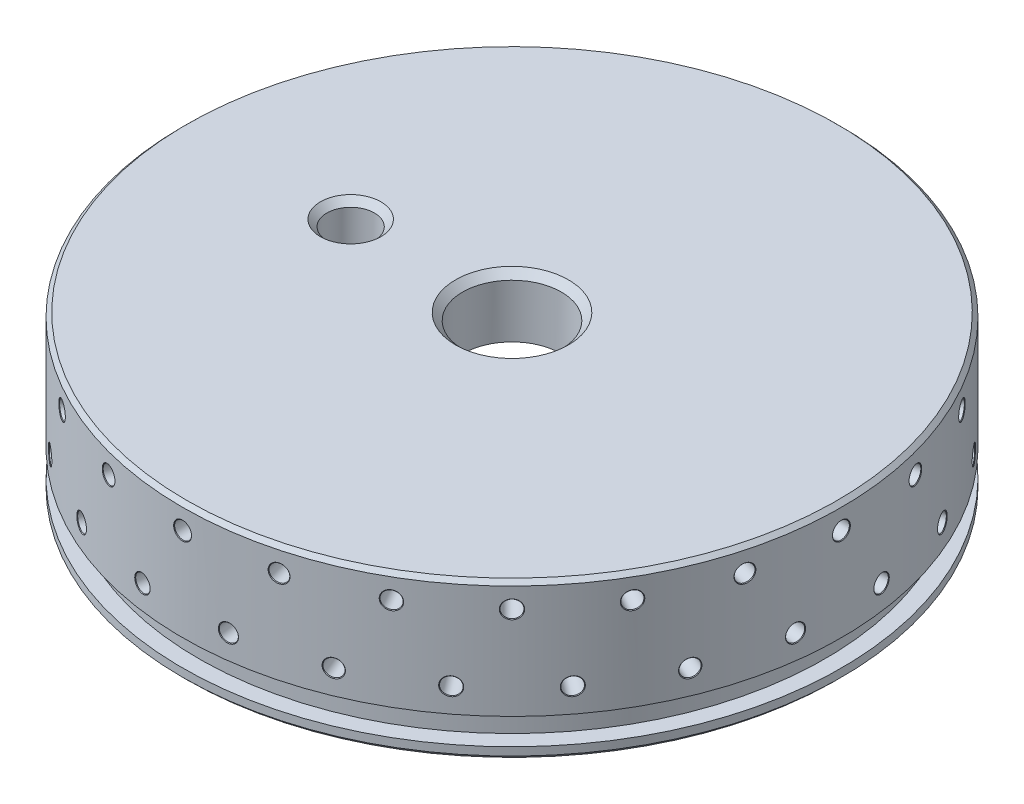
SolidWorks part; units mm, degrees
material "AW-6082-T6 (PA4)"
ref_plane "Płaszczyzna przednia" through (0, 0, 0) normal (0, 0, 1) x (1, 0, 0)
ref_plane "Płaszczyzna górna" through (0, 0, 0) normal (0, 1, 0) x (1, 0, 0)
ref_plane "Płaszczyzna prawa" through (0, 0, 0) normal (1, 0, 0) x (0, 0, -1)
sketch "Szkic1" plane through (0, 0, 0) normal (0, 1, 0) x (1, 0, 0)
  circle A0 centre (0, 0) radius 81.7
  dimension "D1" = 163.4
extrude "Dodanie-wyciągnięcie1" add sketch "Szkic1" along normal blind 38.5
ref_plane "Płaszczyzna1" through (0, 0, -81.7) normal (0, 0, -1) x (-1, 0, 0)
ref_plane "Płaszczyzna2" through (10.664, 0, -81.001) normal (0.1305, 0, -0.9914) x (0, -1, 0)
hole_wizard "Otwór gwintowany M51" positions "Szkic2" profile "Szkic3" hole size "M5" standard "ISO"
sketch "Szkic2" plane through (0, 0, -81.7) normal (0, 0, -1) x (-1, 0, 0)
  line L0 (81.7, 0) -> (81.7, 38.5) construction
  line L1 (-81.7, 38.5) -> (-81.7, 0) construction
  line L2 (81.7, 0) -> (81.7, 38.5)
  line L3 (-81.7, 38.5) -> (-81.7, 0)
  line L4 (0, 51.4702) -> (0, -13.4001) construction
  line L5 (81.7, 38.5) -> (-81.7, 38.5) construction
  point P11 (0, 32.5)
  dimension "D1" = 6
sketch "Szkic3" plane through (0, 32.5, -81.7) normal (1, 0, 0) x (0, 1, 0)
  line L0 (0, 0) -> (0, 9.2618)
  line L1 (0, 9.2618) -> (2.1, 8)
  line L2 (2.1, 8) -> (2.1, 0.15)
  line L3 (2.1, 0.15) -> (2.25, 0)
  line L5 (2.25, 0) -> (0, 0)
  line L6 (-2.1, 0.15) -> (-2.25, 0) construction
  line L10 (0, 9.2618) -> (-2.1, 8) construction
  line L11 (0, -6.35) -> (0, 107.95) construction
  dimension "Średnica otworu" = 4.2
  dimension "Głębokośc otworu" = 8
  dimension "Średnica zewnętrznego pogłębienia stożkowego" = 4.5
  dimension "Kąt zewnętrznego pogłębienia stożkowego" = 90
  dimension "Kąt wiertła" = 118
hole_wizard "Otwór gwintowany M52" positions "Szkic6" profile "Szkic7" hole size "M5" standard "ISO"
sketch "Szkic6" plane through (10.664, 0, -81.001) normal (0.1305, 0, -0.9914) x (0, -1, 0)
  line L0 (-38.5, -81.7) -> (0, -81.7) construction
  line L1 (0, 81.7) -> (-38.5, 81.7) construction
  line L2 (-38.5, -81.7) -> (0, -81.7)
  line L3 (0, 81.7) -> (-38.5, 81.7)
  line L4 (-54.6249, 0) -> (16.9218, 0) construction
  ellipse E0 centre (-32.5, 10.6444) end of major axis (-30.4, 10.6444) minor radius 2.082 construction
  point P10 (-15.5, 0)
  dimension "D1" = 17
sketch "Szkic7" plane through (10.664, 15.5, -81.001) normal (0, 1, 0) x (-0.9914, 0, -0.1305)
  line L0 (0, 0) -> (0, 9.2618)
  line L1 (0, 9.2618) -> (2.1, 8)
  line L2 (2.1, 8) -> (2.1, 0.15)
  line L3 (2.1, 0.15) -> (2.25, 0)
  line L5 (2.25, 0) -> (0, 0)
  line L6 (-2.1, 0.15) -> (-2.25, 0) construction
  line L10 (0, 9.2618) -> (-2.1, 8) construction
  line L11 (0, -6.35) -> (0, 107.95) construction
  dimension "Średnica otworu" = 4.2
  dimension "Głębokośc otworu" = 8
  dimension "Średnica zewnętrznego pogłębienia stożkowego" = 4.5
  dimension "Kąt zewnętrznego pogłębienia stożkowego" = 90
  dimension "Kąt wiertła" = 118
pattern_circular "Szyk kołowy1" count 24 over 360 about axis through (0, 38.5, 0) along (0, -1, 0) of "Otwór gwintowany M51", "Otwór gwintowany M52"
sketch "Szkic8" plane through (0, 0, 0) normal (0, 0, 1) x (1, 0, 0)
  line L0 (-81.7, 30.25) -> (-81.7, 0) construction
  line L1 (-81.7, 30.25) -> (-81.7, 0)
  line L2 (-81.7, 0) -> (81.7, 0) construction
  line L3 (-81.7, 9.5) -> (-77.7, 9.5)
  line L4 (-81.7, 9.5) -> (-81.7, 3)
  line L5 (-81.7, 3) -> (-77.7, 3)
  line L6 (-77.7, 9.5) -> (-77.7, 3)
  line L8 (0, 56.0732) -> (0, -20.5484) construction
  line L9 (81.7, 0) -> (81.7, 30.25) construction
  dimension "D1" = 4
  dimension "D2" = 6.5
  dimension "D3" = 3
revolve "Wycięcie-obrót1" cut sketch "Szkic8" angle 360 about L8 region at (-79.7, 6.25, 0)
sketch "Szkic9" plane through (0, 0, 0) normal (0, 0, 1) x (1, 0, 0)
  line L0 (0, -10.2266) -> (0, 51.1756) construction
  line L1 (-81.7, 0) -> (81.7, 0) construction
  line L2 (0, 0) -> (-66.7, 0)
  line L3 (0, 0) -> (0, 23.5)
  line L4 (0, 23.5) -> (-66.7, 23.5)
  line L5 (-66.7, 0) -> (-66.7, 23.5)
  line L6 (-81.7, 30.2501) -> (-81.7, 9.5) construction
  line L7 (-81.7, 30.2501) -> (-81.7, 9.5)
  line L8 (-73.7, 34.6) -> (-73.7, 30.4) construction
  line L9 (81.7, 38.5) -> (-81.7, 38.5) construction
  line L10 (81.7, 38.5) -> (-81.7, 38.5)
  dimension "D1" = 15
  dimension "D2" = 7
  dimension "D3" = 15
revolve "Wycięcie-obrót2" cut sketch "Szkic9" angle 360 about L0 region at (-33.35, 11.75, 0)
chamfer "Sfazowanie1" distance 1 angle 45 3 edges at (0, 0, -66.7) (0, 0, 81.7) (0, 38.5, 81.7)
hole_wizard "Otwór gwintowany G3/41" positions "Szkic10" profile "Szkic11" tap size "G3/4" standard "ISO" end condition up to next
sketch "Szkic10" plane through (0, 38.5, 0) normal (0, 1, 0) x (1, 0, 0)
  point P0 (0, 0)
sketch "Szkic11" plane through (0, 38.5, 0) normal (1, 0, 0) x (0, 0, 1)
  line L0 (0, 0) -> (0, 15)
  line L1 (0, 15) -> (12.25, 15)
  line L2 (12.25, 15) -> (12.25, 1.75)
  line L3 (12.25, 1.75) -> (14, 0)
  line L5 (14, 0) -> (0, 0)
  line L6 (-12.25, 1.75) -> (-14, 0) construction
  line L11 (0, -6.35) -> (0, 107.95) construction
  dimension "Średnica otworu gwintowanego na wylot" = 24.5
  dimension "Głębokość otworu gwintowanego na wylot" = 15
  dimension "Średnica zewnętrznego pogłębienia stożkowego" = 28
  dimension "Kąt zewnętrznego pogłębienia stożkowego" = 90
cosmetic thread "Gwint otworu1" parameters "D2"=26.441
hole_wizard "Otwór gwintowany G1/41" positions "Szkic12" profile "Szkic13" tap size "G1/4" standard "ISO" end condition up to next
sketch "Szkic12" plane through (0, 38.5, 0) normal (0, 1, 0) x (1, 0, 0)
  line L0 (0, 0) -> (-109.5648, 0) construction
  point P0 (-40, 0)
  dimension "D1" = 40
sketch "Szkic13" plane through (-40, 38.5, 0) normal (1, 0, 0) x (0, 0, 1)
  line L0 (0, 0) -> (0, 15)
  line L1 (0, 15) -> (5.9, 15)
  line L2 (5.9, 15) -> (5.9, 1.6)
  line L3 (5.9, 1.6) -> (7.5, 0)
  line L5 (7.5, 0) -> (0, 0)
  line L6 (-5.9, 1.6) -> (-7.5, 0) construction
  line L11 (0, -6.35) -> (0, 107.95) construction
  dimension "Średnica otworu gwintowanego na wylot" = 11.8
  dimension "Głębokość otworu gwintowanego na wylot" = 15
  dimension "Średnica zewnętrznego pogłębienia stożkowego" = 15
  dimension "Kąt zewnętrznego pogłębienia stożkowego" = 90
cosmetic thread "Gwint otworu2" parameters "D2"=13.157
